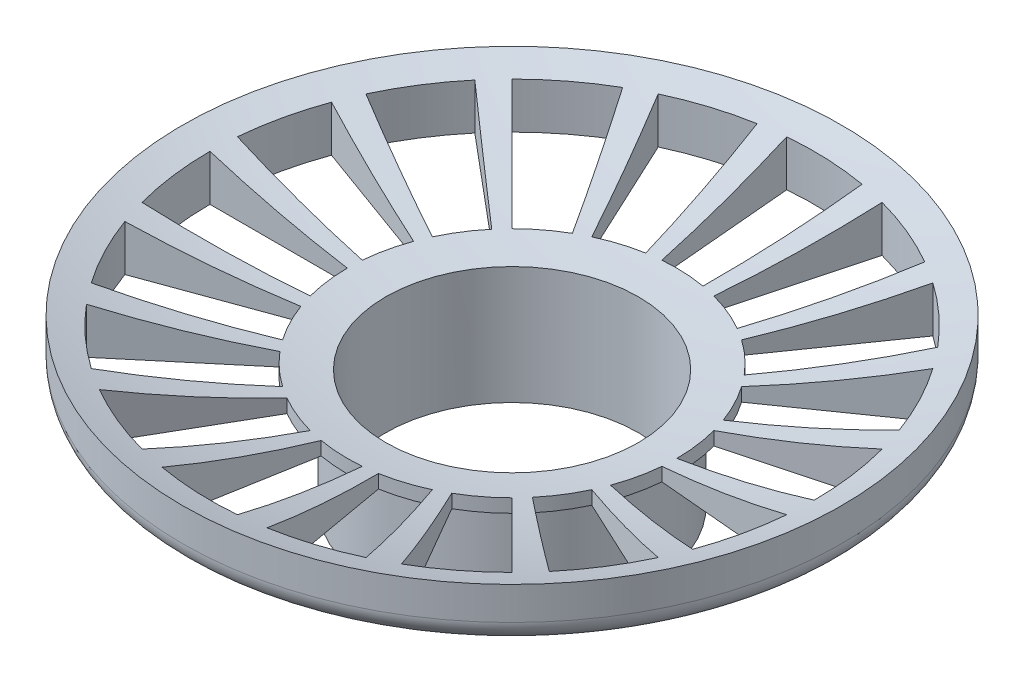
SolidWorks part; units mm, degrees
ref_plane "Front Plane" through (0, 0, 0) normal (0, 0, 1) x (1, 0, 0)
ref_plane "Top Plane" through (0, 0, 0) normal (0, 1, 0) x (1, 0, 0)
ref_plane "Right Plane" through (0, 0, 0) normal (1, 0, 0) x (0, 0, -1)
sketch "Sketch1" plane through (0, 0, 0) normal (0, 1, 0) x (1, 0, 0)
  circle A0 centre (0, 0) radius 12.5
  dimension "D1" = 25
extrude "Boss-Extrude1" add sketch "Sketch1" along normal blind 10
sketch "Sketch3" plane through (0, 10, 0) normal (0, 1, 0) x (1, 0, 0)
  circle A0 centre (0, 0) radius 30
  dimension "D1" = 60
extrude "Boss-Extrude2" add sketch "Sketch3" along normal blind 5
dome "Dome1" faces to dome 1 distance 5 reverse direction yes elliptical dome no face at (0, 15, 30) parameters "D1"=5
sketch "Sketch8" plane through (0, 0, 0) normal (0, -1, 0) x (1, 0, 0)
  circle A0 centre (0, 0) radius 11.5
  dimension "D1" = 23
extrude "Cut-Extrude3" cut sketch "Sketch8" against normal through all
sketch "Sketch9" plane through (0, 10, 0) normal (0, -1, 0) x (1, 0, 0)
  line L0 (-15, 0) -> (-27.5, 0)
  line L1 (-14.4889, 3.8823) -> (-26.563, 7.1175)
  line L2 (0, 0) -> (-14.4889, 3.8823) construction
  line L3 (-12.2873, 8.6036) -> (-22.5267, 15.7734)
  line L4 (-14.0954, 5.1303) -> (-25.8415, 9.4056)
  line L5 (-8.6036, 12.2873) -> (-15.7734, 22.5267)
  line L6 (-11.4907, 9.6418) -> (-21.0662, 17.6767)
  line L7 (-3.8823, 14.4889) -> (-7.1175, 26.563)
  line L8 (-7.5, 12.9904) -> (-13.75, 23.8157)
  line L9 (1.3073, 14.9429) -> (2.3968, 27.3954)
  line L10 (-2.6047, 14.7721) -> (-4.7753, 27.0822)
  line L11 (6.3393, 13.5946) -> (11.622, 24.9235)
  line L12 (2.6047, 14.7721) -> (4.7753, 27.0822)
  line L13 (10.6066, 10.6066) -> (19.4454, 19.4454)
  line L14 (7.5, 12.9904) -> (13.75, 23.8157)
  line L15 (13.5946, 6.3393) -> (24.9235, 11.622)
  line L16 (11.4907, 9.6418) -> (21.0662, 17.6767)
  line L17 (14.9429, 1.3073) -> (27.3954, 2.3968)
  line L18 (14.0954, 5.1303) -> (25.8415, 9.4056)
  line L19 (14.4889, -3.8823) -> (26.563, -7.1175)
  line L20 (15, 0) -> (27.5, 0)
  line L21 (12.2873, -8.6036) -> (22.5267, -15.7734)
  line L22 (14.0954, -5.1303) -> (25.8415, -9.4056)
  line L23 (8.6036, -12.2873) -> (15.7734, -22.5267)
  line L24 (11.4907, -9.6418) -> (21.0662, -17.6767)
  line L25 (3.8823, -14.4889) -> (7.1175, -26.563)
  line L26 (7.5, -12.9904) -> (13.75, -23.8157)
  line L27 (-1.3073, -14.9429) -> (-2.3968, -27.3954)
  line L28 (2.6047, -14.7721) -> (4.7753, -27.0822)
  line L29 (-6.3393, -13.5946) -> (-11.622, -24.9235)
  line L30 (-2.6047, -14.7721) -> (-4.7753, -27.0822)
  line L31 (-10.6066, -10.6066) -> (-19.4454, -19.4454)
  line L32 (-7.5, -12.9904) -> (-13.75, -23.8157)
  line L33 (-13.5946, -6.3393) -> (-24.9235, -11.622)
  line L34 (-11.4907, -9.6418) -> (-21.0662, -17.6767)
  line L35 (-14.9429, -1.3073) -> (-27.3954, -2.3968)
  line L36 (-14.0954, -5.1303) -> (-25.8415, -9.4056)
  arc A0 (-14.4889, 3.8823) -> (-15, 0) centre (0, 0) ccw
  arc A1 (-26.563, 7.1175) -> (-27.5, 0) centre (0, 0) ccw
  circle A2 centre (0, 0) radius 30 construction
  circle A4 centre (0, 0) radius 12.5 construction
  arc A5 (-27.5, 0) -> (-26.563, 7.1175) centre (0, 0) ccw construction
  arc A6 (-15, 0) -> (-14.4889, 3.8823) centre (0, 0) ccw construction
  arc A7 (-22.5267, 15.7734) -> (-25.8415, 9.4056) centre (0, 0) ccw
  arc A8 (-12.2873, 8.6036) -> (-14.0954, 5.1303) centre (0, 0) ccw
  arc A9 (-15.7734, 22.5267) -> (-21.0662, 17.6767) centre (0, 0) ccw
  arc A10 (-8.6036, 12.2873) -> (-11.4907, 9.6418) centre (0, 0) ccw
  arc A11 (-7.1175, 26.563) -> (-13.75, 23.8157) centre (0, 0) ccw
  arc A12 (-3.8823, 14.4889) -> (-7.5, 12.9904) centre (0, 0) ccw
  arc A13 (2.3968, 27.3954) -> (-4.7753, 27.0822) centre (0, 0) ccw
  arc A14 (1.3073, 14.9429) -> (-2.6047, 14.7721) centre (0, 0) ccw
  arc A15 (11.622, 24.9235) -> (4.7753, 27.0822) centre (0, 0) ccw
  arc A16 (6.3393, 13.5946) -> (2.6047, 14.7721) centre (0, 0) ccw
  arc A17 (19.4454, 19.4454) -> (13.75, 23.8157) centre (0, 0) ccw
  arc A18 (10.6066, 10.6066) -> (7.5, 12.9904) centre (0, 0) ccw
  arc A19 (24.9235, 11.622) -> (21.0662, 17.6767) centre (0, 0) ccw
  arc A20 (13.5946, 6.3393) -> (11.4907, 9.6418) centre (0, 0) ccw
  arc A21 (27.3954, 2.3968) -> (25.8415, 9.4056) centre (0, 0) ccw
  arc A22 (14.9429, 1.3073) -> (14.0954, 5.1303) centre (0, 0) ccw
  arc A23 (26.563, -7.1175) -> (27.5, 0) centre (0, 0) ccw
  arc A24 (14.4889, -3.8823) -> (15, 0) centre (0, 0) ccw
  arc A25 (22.5267, -15.7734) -> (25.8415, -9.4056) centre (0, 0) ccw
  arc A26 (12.2873, -8.6036) -> (14.0954, -5.1303) centre (0, 0) ccw
  arc A27 (15.7734, -22.5267) -> (21.0662, -17.6767) centre (0, 0) ccw
  arc A28 (8.6036, -12.2873) -> (11.4907, -9.6418) centre (0, 0) ccw
  arc A29 (7.1175, -26.563) -> (13.75, -23.8157) centre (0, 0) ccw
  arc A30 (3.8823, -14.4889) -> (7.5, -12.9904) centre (0, 0) ccw
  arc A31 (-2.3968, -27.3954) -> (4.7753, -27.0822) centre (0, 0) ccw
  arc A32 (-1.3073, -14.9429) -> (2.6047, -14.7721) centre (0, 0) ccw
  arc A33 (-11.622, -24.9235) -> (-4.7753, -27.0822) centre (0, 0) ccw
  arc A34 (-6.3393, -13.5946) -> (-2.6047, -14.7721) centre (0, 0) ccw
  arc A35 (-19.4454, -19.4454) -> (-13.75, -23.8157) centre (0, 0) ccw
  arc A36 (-10.6066, -10.6066) -> (-7.5, -12.9904) centre (0, 0) ccw
  arc A37 (-24.9235, -11.622) -> (-21.0662, -17.6767) centre (0, 0) ccw
  arc A38 (-13.5946, -6.3393) -> (-11.4907, -9.6418) centre (0, 0) ccw
  arc A39 (-27.3954, -2.3968) -> (-25.8415, -9.4056) centre (0, 0) ccw
  arc A40 (-14.9429, -1.3073) -> (-14.0954, -5.1303) centre (0, 0) ccw
  dimension "D1" = 2.5
  dimension "D2" = 2.5
  dimension "D3" = 15
  dimension "D4" = 18
extrude "Cut-Extrude4" cut sketch "Sketch9" against normal through all
fillet "Fillet2" radius 2 1 edges at (0, 10, 30)
